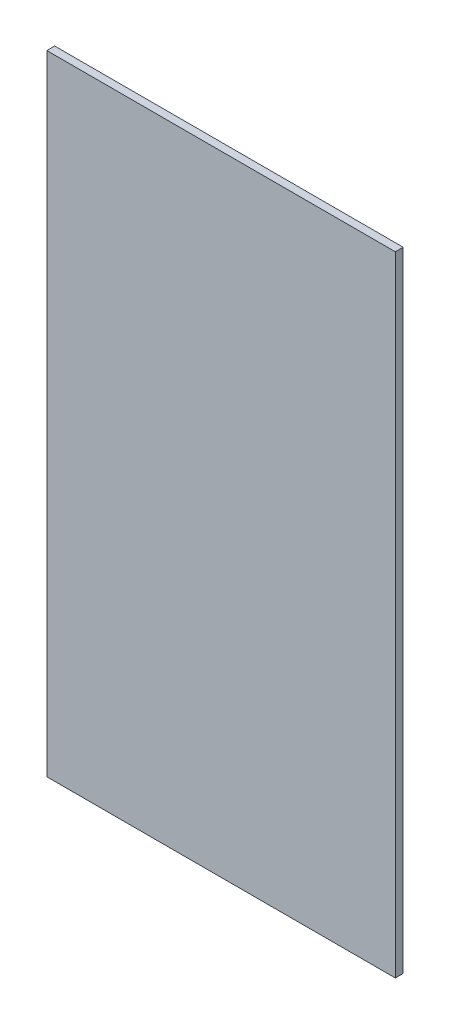
SolidWorks part; units mm, degrees
ref_plane "Plan de face" through (0, 0, 0) normal (0, 0, 1) x (1, 0, 0)
ref_plane "Plan de dessus" through (0, 0, 0) normal (0, 1, 0) x (1, 0, 0)
ref_plane "Plan de droite" through (0, 0, 0) normal (1, 0, 0) x (0, 0, -1)
sketch "Esquisse1" plane through (0, 0, 0) normal (0, 0, 1) x (1, 0, 0)
  line L1 (-62.9102, 49.3173) -> (70.0898, 49.3173)
  line L2 (-62.9102, 49.3173) -> (-62.9102, -190.6827)
  line L3 (-62.9102, -190.6827) -> (70.0898, -190.6827)
  line L4 (70.0898, 49.3173) -> (70.0898, -190.6827)
  dimension "D1" = 133
  dimension "D2" = 240
extrude "Boss.-Extru.1" add sketch "Esquisse1" along normal blind 3
equation "\"D1@Esquisse1\"=\"LargeurBoite\" - \"LargeurGauche\" + \"EpaisseurPlaque\""
equation "\"ProfondeurBoite\"=460"
equation "\"LongueurSyphon\"=170"
equation "\"LargeurSyphon\"=120"
equation "\"EpaisseurPlaque\"= 3"
equation "\"HauteurCoteDroit\"= 490"
equation "\"HauteurCoteGauche\"= 540"
equation "\"HauteurSolSyphon\"= 300"
equation "\"HauteurSyphon\"=\"HauteurCoteGauche\"-\"HauteurSolSyphon\""
equation "\"D2@Esquisse1\" = \"HauteurSyphon\""
equation "\"LargeurDroite\"=10"
equation "\"LargeurGauche\"=150"
equation "\"LargeurBoite\"= \"LargeurDroite\" + \"LargeurGauche\" + \"LargeurSyphon\""
